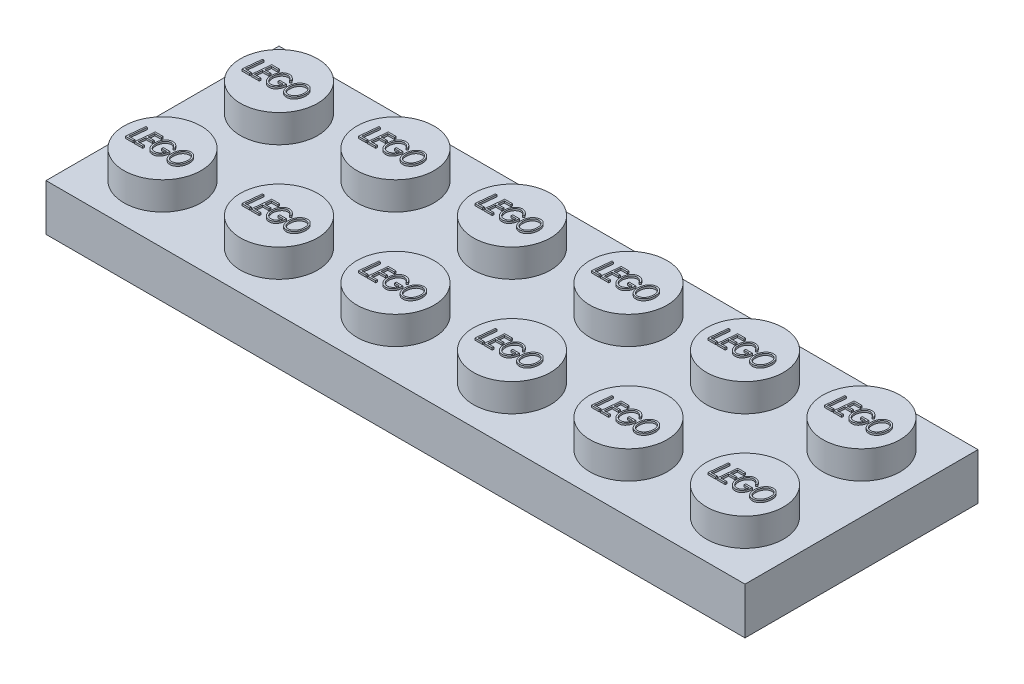
SolidWorks part; units mm, degrees
ref_plane "Front Plane" through (0, 0, 0) normal (0, 0, 1) x (1, 0, 0)
ref_plane "Top Plane" through (0, 0, 0) normal (0, 1, 0) x (1, 0, 0)
ref_plane "Right Plane" through (0, 0, 0) normal (1, 0, 0) x (0, 0, -1)
sketch "Sketch2" plane through (0, 0, 0) normal (0, 1, 0) x (1, 0, 0)
  line L0 (-49.4831, 8.7234) -> (-1.8581, 8.7234)
  line L1 (-1.8581, 8.7234) -> (-1.8581, -7.1516)
  line L2 (-1.8581, -7.1516) -> (-49.4831, -7.1516)
  line L3 (-49.4831, -7.1516) -> (-49.4831, 8.7234)
  dimension "D1" = 47.625
  dimension "D2" = 15.875
extrude "Boss-Extrude3" add sketch "Sketch2" along normal blind 3.175
sketch "Sketch3" plane through (0, 3.175, 0) normal (0, 1, 0) x (1, 0, 0)
  line L0 (-49.4831, 8.7234) -> (-49.4831, -7.1516) construction
  line L1 (-1.8581, 8.7234) -> (-49.4831, 8.7234) construction
  circle A0 centre (-45.5144, 4.7546) radius 2.6308
  dimension "D1" = 3.9687
  dimension "D2" = 3.9688
extrude "Boss-Extrude4" add sketch "Sketch3" along normal blind 1.905
pattern_linear "LPattern1" count 6 spacing 7.9375 along (1, 0, 0) count 2 spacing 7.9375 along (0, 0, 1) of "Boss-Extrude4"
shell "Shell1" thickness 1.524 removed face at (-25.6706, 0, -0.7859)
sketch "Sketch4" plane through (0, 5.08, 0) normal (0, 1, 0) x (1, 0, 0)
  line L1 (-45.5144, 4.7546) -> (-45.5144, 4.0766) construction
  line L2 (-15.584, 4.0766) -> (-43.6947, 4.0766) construction
  text T0 "<i>LEGO</i>" font "Century Gothic" height 1.27
  point P4 (-13.7644, 4.7546)
  point P9 (-29.6394, 4.0766)
extrude "Boss-Extrude5" add sketch "Sketch4" along normal blind 0.127
pattern_linear "LPattern2" count 4 spacing 7.9375 along (1, 0, 0) count 2 spacing 7.9375 along (0, 0, 1) of "Boss-Extrude5"
pattern_linear "LPattern4" count 3 spacing 7.9375 along (-1, 0, 0) of "Boss-Extrude5", "LPattern2"
sketch "Sketch5" plane through (0, 0, 0) normal (0, -1, 0) x (1, 0, 0)
  circle A2 centre (-9.7956, -0.7859) radius 3.175
  circle A3 centre (-9.7956, -0.7859) radius 2.3876
  dimension "D1" = 6.35
  dimension "D2" = 4.7752
extrude "Boss-Extrude6" add sketch "Sketch5" against normal up to surface (1.651 mm away) up to face at (-37.5769, 1.651, -5.8614)
pattern_linear "LPattern3" count 5 spacing 7.9375 along (-1, 0, 0) of "Boss-Extrude6"
